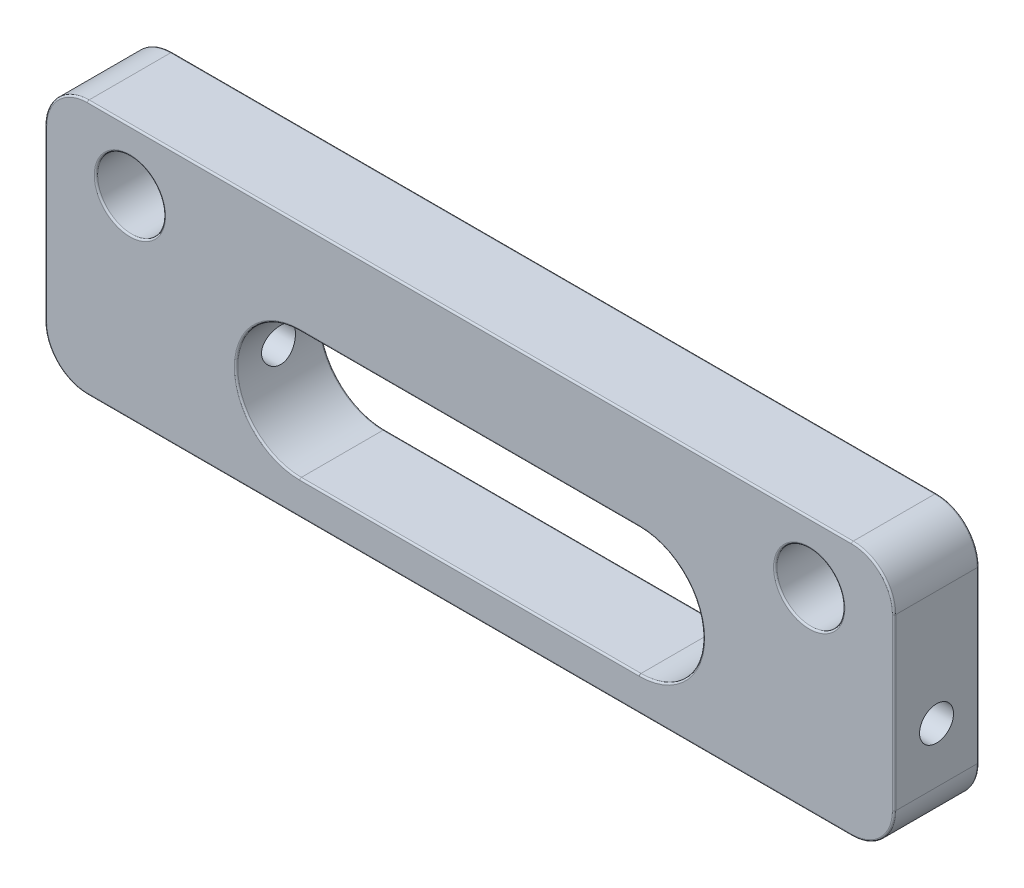
SolidWorks part; units mm, degrees
ref_plane "Ön Düzlem" through (0, 0, 0) normal (0, 0, 1) x (1, 0, 0)
ref_plane "Üst Düzlem" through (0, 0, 0) normal (0, 1, 0) x (1, 0, 0)
ref_plane "Sağ Düzlem" through (0, 0, 0) normal (1, 0, 0) x (0, 0, -1)
sketch "Sketch1" plane through (0, 0, 0) normal (0, 0, 1) x (1, 0, 0)
  line L0 (50, -3.5) -> (-50, -3.5) construction
  line L1 (50, 15) -> (-50, 15)
  line L2 (50, 15) -> (50, -15)
  line L3 (50, -15) -> (-50, -15)
  line L4 (-50, 15) -> (-50, -15)
  line L5 (50, 15) -> (-50, -15) construction
  line L6 (50, -15) -> (-50, 15) construction
  line L7 (20, -3.5) -> (-20, -3.5) construction
  line L8 (20, -11) -> (-20, -11)
  line L9 (20, 4) -> (-20, 4)
  line L10 (0, 0) -> (0, 15) construction
  line L11 (40, -15) -> (40, 15) construction
  arc A0 (20, -11) -> (20, 4) centre (20, -3.5) ccw
  arc A1 (-20, 4) -> (-20, -11) centre (-20, -3.5) ccw
  circle A2 centre (40, 7.8239) radius 4
  circle A3 centre (-40, 7.8239) radius 4
  point P0 (0, 0)
  point P10 (0, -3.5)
  dimension "D6" = 8
  dimension "D1" = 100
  dimension "D2" = 30
  dimension "D3" = 15
  dimension "D4" = 40
  dimension "D5" = 19
  dimension "D8" = 10
extrude "Boss-Extrude1" add sketch "Sketch1" along normal mid plane 10
fillet "Fillet1" radius 5 4 edges at (50, -15, 0) (50, 15, 0) (-50, -15, 0) (-50, 15, 0)
fillet "Fillet2" radius 0.2 28 edges at (-44, 7.8239, -5) (-27.5, -3.5, -5) (0, 4, -5) (27.5, -3.5, -5) (0, -11, -5) (48.5355, 13.5355, -5) (0, 15, -5) (-48.5355, 13.5355, -5) (-50, 0, -5) (-48.5355, -13.5355, -5) (0, -15, -5) (48.5355, -13.5355, -5) (50, 0, -5) (44, 7.8239, -5) (-44, 7.8239, 5) (0, 4, 5) (-27.5, -3.5, 5) (0, -11, 5) (27.5, -3.5, 5) (-48.5355, -13.5355, 5) (-50, 0, 5) (-48.5355, 13.5355, 5) (0, 15, 5) (48.5355, 13.5355, 5) (50, 0, 5) (48.5355, -13.5355, 5) (0, -15, 5) (44, 7.8239, 5)
ref_axis "Axis1" through (-40, 7.8239, 4.8) along (0, 0, -1)
ref_plane "Plane1" through (0, -3.5, 0) normal (0, 1, 0) x (1, 0, 0)
ref_axis "Axis2" through (40, 7.8239, 4.8) along (0, 0, -1)
sketch "Sketch3" plane through (50, 0, 0) normal (1, 0, 0) x (0, 0, -1)
  line L0 (5.28, -3.5) -> (-5.28, -3.5) construction
  circle A0 centre (0, -3.5) radius 2
  dimension "D1" = 4
extrude "Cut-Extrude1" cut sketch "Sketch3" against normal through all
